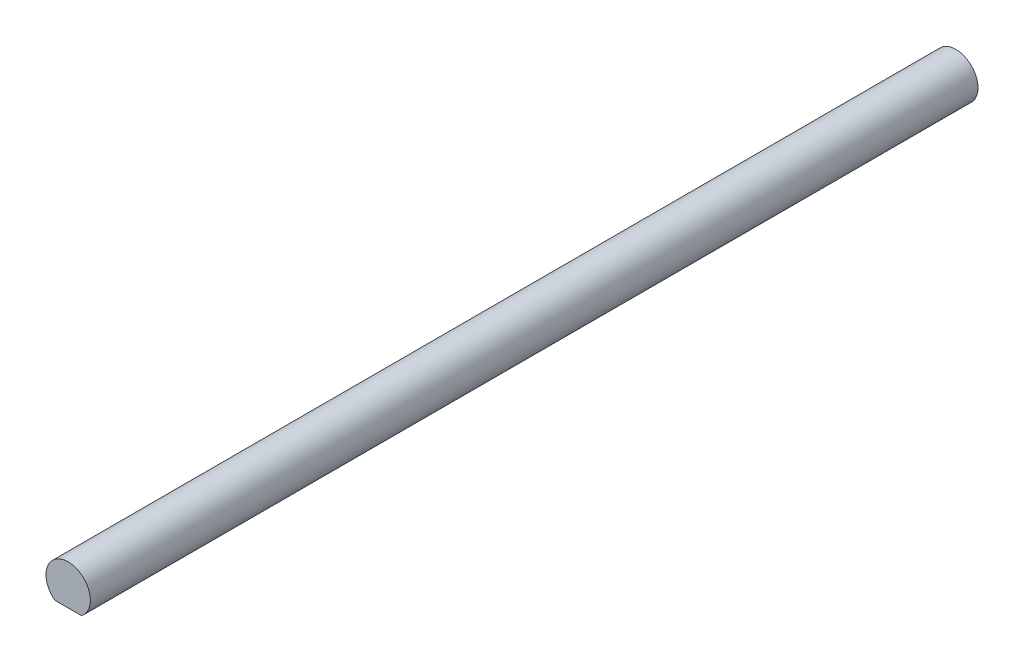
SolidWorks part; units mm, degrees
ref_plane "Front Plane" through (0, 0, 0) normal (0, 0, 1) x (1, 0, 0)
ref_plane "Top Plane" through (0, 0, 0) normal (0, 1, 0) x (1, 0, 0)
ref_plane "Right Plane" through (0, 0, 0) normal (1, 0, 0) x (0, 0, -1)
sketch "Sketch1" plane through (0, 0, 0) normal (0, 0, 1) x (1, 0, 0)
  line L0 (-1.905, -2.54) -> (1.905, -2.54)
  line L1 (0, 3.175) -> (0, -2.54) construction
  circle A0 centre (0, 0) radius 3.175
  dimension "D1" = 6.35
  dimension "D2" = 5.715
extrude "Boss-Extrude1" add sketch "Sketch1" along normal blind 63.5 and the other way blind 63.5 contours L1 A0 L0 | A0 L1 L0 region at (-1.3817, 0.1535, 0) region at (1.3817, 0.1535, 0)
ref_axis "Axis1" through (0, 0, -63.5) along (0, 0, 1)
